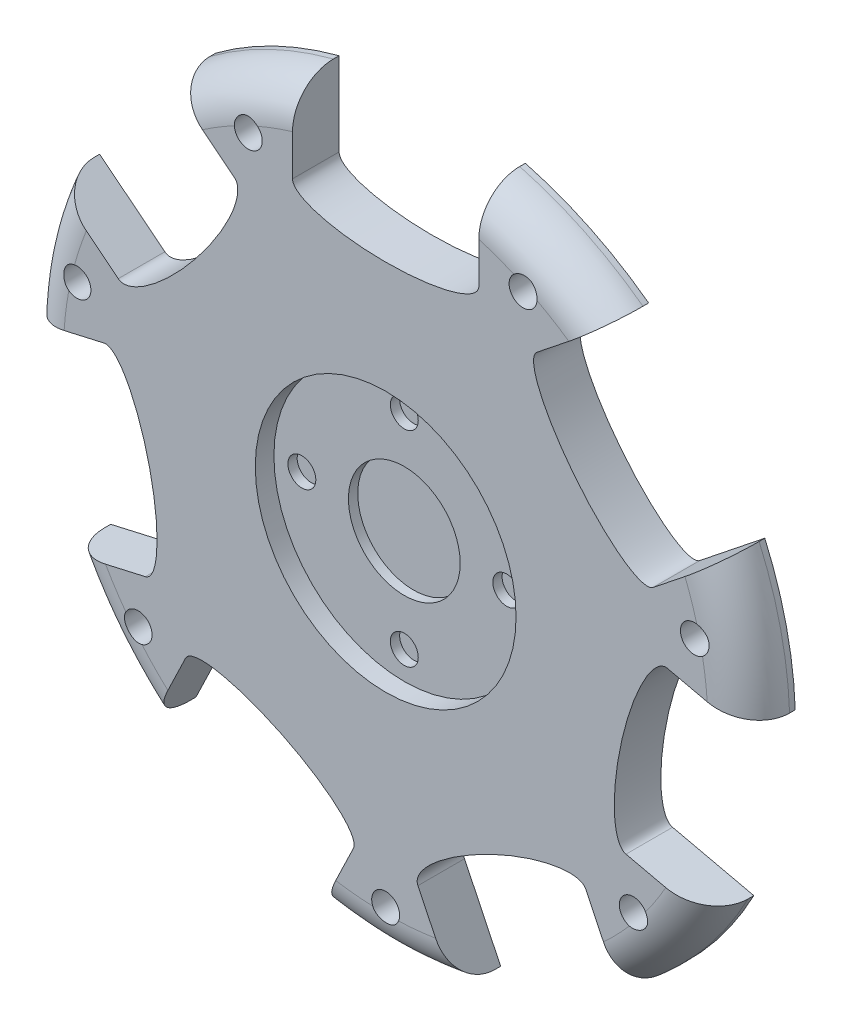
SolidWorks part; units mm, degrees
ref_plane "Front" through (0, 0, 0) normal (0, 0, 1) x (1, 0, 0)
ref_plane "Top" through (0, 0, 0) normal (0, 1, 0) x (1, 0, 0)
ref_plane "Right" through (0, 0, 0) normal (1, 0, 0) x (0, 0, -1)
sketch "草图1" plane through (0, 0, 0) normal (0, 0, 1) x (1, 0, 0)
  line L0 (0, -14.6841) -> (0, 53.021) construction
  line L1 (-15.8033, 33.5) -> (15.016, 33.5) construction
  line L2 (-10, 41) -> (10, 41) construction
  line L5 (-10, 31.5) -> (10, 31.5) construction
  line L6 (-10, 31.5) -> (-10, 26) construction
  line L7 (-10, 26) -> (10, 26) construction
  line L8 (10, 31.5) -> (10, 26) construction
  line L9 (-10, 28.75) -> (-10, 37.6962)
  line L10 (10, 28.75) -> (10, 37.6962)
  line L11 (16.2428, 25.7436) -> (23.2371, 31.3215)
  line L12 (28.7126, 10.107) -> (35.7069, 15.6849)
  line L13 (30.2544, 3.3518) -> (38.9762, 1.3611)
  line L14 (25.804, -16.1468) -> (34.5258, -18.1375)
  line L15 (21.4838, -21.564) -> (25.3654, -29.6242)
  line L16 (3.4645, -30.2417) -> (7.3461, -38.3019)
  line L17 (-3.4645, -30.2417) -> (-7.3461, -38.3019)
  line L18 (-21.4838, -21.564) -> (-25.3654, -29.6242)
  line L19 (-25.804, -16.1468) -> (-34.5258, -18.1375)
  line L20 (-30.2544, 3.3518) -> (-38.9762, 1.3611)
  line L21 (-28.7126, 10.107) -> (-35.7069, 15.6849)
  line L22 (-16.2428, 25.7436) -> (-23.2371, 31.3215)
  arc A0 (-10, 37.6962) -> (-23.2371, 31.3215) centre (0, 0) ccw
  arc A1 (-35.7069, 15.6849) -> (-38.9762, 1.3611) centre (0, 0) ccw
  arc A2 (-34.5258, -18.1375) -> (-25.3654, -29.6242) centre (0, 0) ccw
  arc A3 (-7.3461, -38.3019) -> (7.3461, -38.3019) centre (0, 0) ccw
  arc A4 (25.3654, -29.6242) -> (34.5258, -18.1375) centre (0, 0) ccw
  arc A5 (38.9762, 1.3611) -> (35.7069, 15.6849) centre (0, 0) ccw
  arc A6 (23.2371, 31.3215) -> (10, 37.6962) centre (0, 0) ccw
  ellipse E0 centre (0, 28.75) end of major axis (10, 28.75) minor radius 2.75 (-10, 28.75) -> (10, 28.75) ccw
  ellipse E1 centre (22.4777, 17.9253) end of major axis (28.7126, 10.107) minor radius 2.75 (16.2428, 25.7436) -> (28.7126, 10.107) ccw
  ellipse E2 centre (28.0292, -6.3975) end of major axis (25.804, -16.1468) minor radius 2.75 (30.2544, 3.3518) -> (25.804, -16.1468) ccw
  ellipse E3 centre (12.4742, -25.9029) end of major axis (3.4645, -30.2417) minor radius 2.75 (21.4838, -21.564) -> (3.4645, -30.2417) ccw
  ellipse E4 centre (-12.4742, -25.9029) end of major axis (-21.4838, -21.564) minor radius 2.75 (-3.4645, -30.2417) -> (-21.4838, -21.564) ccw
  ellipse E5 centre (-28.0292, -6.3975) end of major axis (-30.2544, 3.3518) minor radius 2.75 (-25.804, -16.1468) -> (-30.2544, 3.3518) ccw
  ellipse E6 centre (-22.4777, 17.9253) end of major axis (-16.2428, 25.7436) minor radius 2.75 (-28.7126, 10.107) -> (-16.2428, 25.7436) ccw
  point P79 (0, 0)
  dimension "D1" = 78
  dimension "D2" = 20
  dimension "D3" = 10
  dimension "D4" = 2
  dimension "D5" = 7.5
  dimension "D6" = 41
  dimension "D7" = 7
extrude "凸台-拉伸2" add sketch "草图1" along normal blind 5
sketch "草图3" plane through (0, 0, 5) normal (0, 0, 1) x (1, 0, 0)
  line L0 (0, 0) -> (16.9215, 35.1378) construction
  circle A0 centre (0, 0) radius 11 construction
  circle A1 centre (0, 11) radius 1.5
  circle A2 centre (11, 0) radius 1.5
  circle A3 centre (0, -11) radius 1.5
  circle A4 centre (-11, 0) radius 1.5
  circle A5 centre (0, 0) radius 6
  circle A6 centre (0, 0) radius 34 construction
  circle A7 centre (14.752, 30.6329) radius 1.5
  arc A8 (23.2371, 31.3215) -> (10, 37.6962) centre (0, 0) ccw construction
  circle A9 centre (33.1475, 7.5657) radius 1.5
  circle A10 centre (26.5823, -21.1987) radius 1.5
  circle A11 centre (0, -34) radius 1.5
  circle A12 centre (-26.5823, -21.1987) radius 1.5
  circle A13 centre (-33.1475, 7.5657) radius 1.5
  circle A14 centre (-14.752, 30.6329) radius 1.5
  point P14 (0, 0)
  point P35 (0, 0)
  dimension "D1" = 4
  dimension "D2" = 3
  dimension "D3" = 68
  dimension "D4" = 7
extrude "切除-拉伸2" cut sketch "草图3" against normal blind 3
sketch "草图4" plane through (0, 0, 5) normal (0, 0, 1) x (1, 0, 0)
  circle A0 centre (0, 0) radius 14
extrude "切除-拉伸3" cut sketch "草图4" against normal blind 2
scale "缩放比例1" scale about centroid uniform scaling yes scale factor 0.683
fillet "圆角2" radius 3 7 edges at (25.9692, 5.9273, 4.1623) (20.8256, -16.6079, 4.1623) (0, -26.637, 4.1623) (11.5574, 23.9991, 4.1623) (-11.5574, 23.9991, 4.1623) (-25.9692, 5.9273, 4.1623) (-20.8256, -16.6079, 4.1623)
